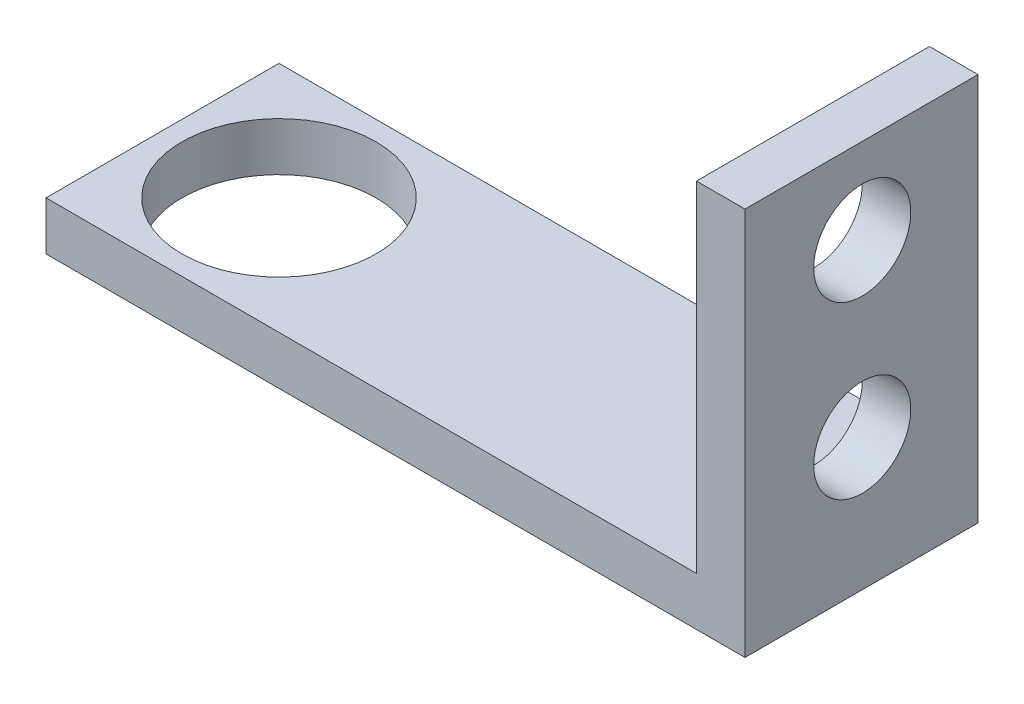
SolidWorks part; units mm, degrees
other "Markup1"
sketch "Sketch8" plane through (-25.4, 12.7, -7.62) normal (0, 1, 0) x (1, 0, 0)
ref_plane "Front Plane" through (0, 0, 0) normal (0, 0, 1) x (1, 0, 0)
ref_plane "Top Plane" through (0, 0, 0) normal (0, 1, 0) x (1, 0, 0)
ref_plane "Right Plane" through (0, 0, 0) normal (1, 0, 0) x (0, 0, -1)
sketch "Sketch1" plane through (0, 0, 0) normal (0, 1, 0) x (1, 0, 0)
  line L1 (0, 0) -> (-25.4, 0)
  line L2 (0, 0) -> (0, 7.62)
  line L3 (0, 7.62) -> (-25.4, 7.62)
  line L4 (-25.4, 0) -> (-25.4, 7.62)
  line L5 (0, 7.62) -> (-1.5875, 7.62)
  line L6 (0, 7.62) -> (0, 0)
  line L7 (0, 0) -> (-1.5875, 0)
  line L8 (-1.5875, 7.62) -> (-1.5875, 0)
  dimension "D1" = 25.4
  dimension "D2" = 1.5875
  dimension "D3" = 7.62
extrude "Boss-Extrude1" add sketch "Sketch1" along normal blind 1.5875 contours L8 L3 L4 L1 region at (-13.4937, 0, -3.81)
extrude "Boss-Extrude2" add sketch "Sketch1<4>" along normal blind 12.7 contours L3 L8 L1 L2 region at (-0.7937, 0, -3.81)
sketch "Sketch1<4>" plane through (0, 0, 0) normal (0, 1, 0) x (1, 0, 0) same geometry as "Sketch1"
hole_wizard "1/4 (0.25) Diameter Hole1" positions "Sketch4" profile "Sketch5" hole size "1/4" standard "ANSI Inch" end condition through all
sketch "Sketch4" plane through (0, 0, 0) normal (0, -1, 0) x (-1, 0, 0)
  line L0 (0, 7.62) -> (25.4, 7.62) construction
  line L1 (0, 0) -> (0, 7.62) construction
  point P0 (19.05, 3.81)
  dimension "D1" = 3.81
  dimension "D2" = 19.05
sketch "Sketch5" plane through (-19.05, 0, -3.81) normal (1, 0, 0) x (0, 0, -1)
  line L0 (0, 0) -> (0, 12.7)
  line L1 (0, 12.7) -> (3.175, 12.7)
  line L2 (3.175, 12.7) -> (3.175, 0)
  line L5 (3.175, 0) -> (0, 0)
  line L11 (0, -6.35) -> (0, 107.95) construction
  dimension "Thru Hole Dia." = 6.35
  dimension "Thru Hole Depth" = 12.7
sketch "Sketch7" plane through (0, 1.5875, 0) normal (0, 1, 0) x (1, 0, 0)
  line L0 (-22.86, 7.62) -> (-22.86, 0)
  line L1 (-1.5875, 7.62) -> (-25.4, 7.62) construction
  line L2 (-1.5875, 0) -> (-25.4, 0) construction
  circle A1 centre (-19.05, 3.81) radius 3.175 construction
  dimension "D1" = 3.81
extrude "Cut-Extrude2" cut sketch "Sketch7" against normal blind 1.5875 and the other way through all flip side to cut
hole_wizard "1/8 (0.125) Diameter Hole1" positions "Sketch12" profile "Sketch13" hole size "1/8" standard "ANSI Inch" end condition through all
sketch "Sketch12" plane through (-1.5875, 0, 0) normal (-1, 0, 0) x (0, 0, 1)
  line L2 (-7.62, 12.7) -> (0, 12.7) construction
  point P0 (-3.8347, 9.906)
  point P2 (-3.8347, 4.318)
  point P11 (-3.81, 12.7)
  dimension "D1" = 2.794
  dimension "D2" = 8.382
sketch "Sketch13" plane through (-1.5875, 9.906, -3.8347) normal (0, 1, 0) x (0, 0, 1)
  line L0 (0, 0) -> (0, 1.5875)
  line L1 (0, 1.5875) -> (1.5875, 1.5875)
  line L2 (1.5875, 1.5875) -> (1.5875, 0)
  line L5 (1.5875, 0) -> (0, 0)
  line L11 (0, -6.35) -> (0, 107.95) construction
  dimension "Thru Hole Dia." = 3.175
  dimension "Thru Hole Depth" = 1.5875
